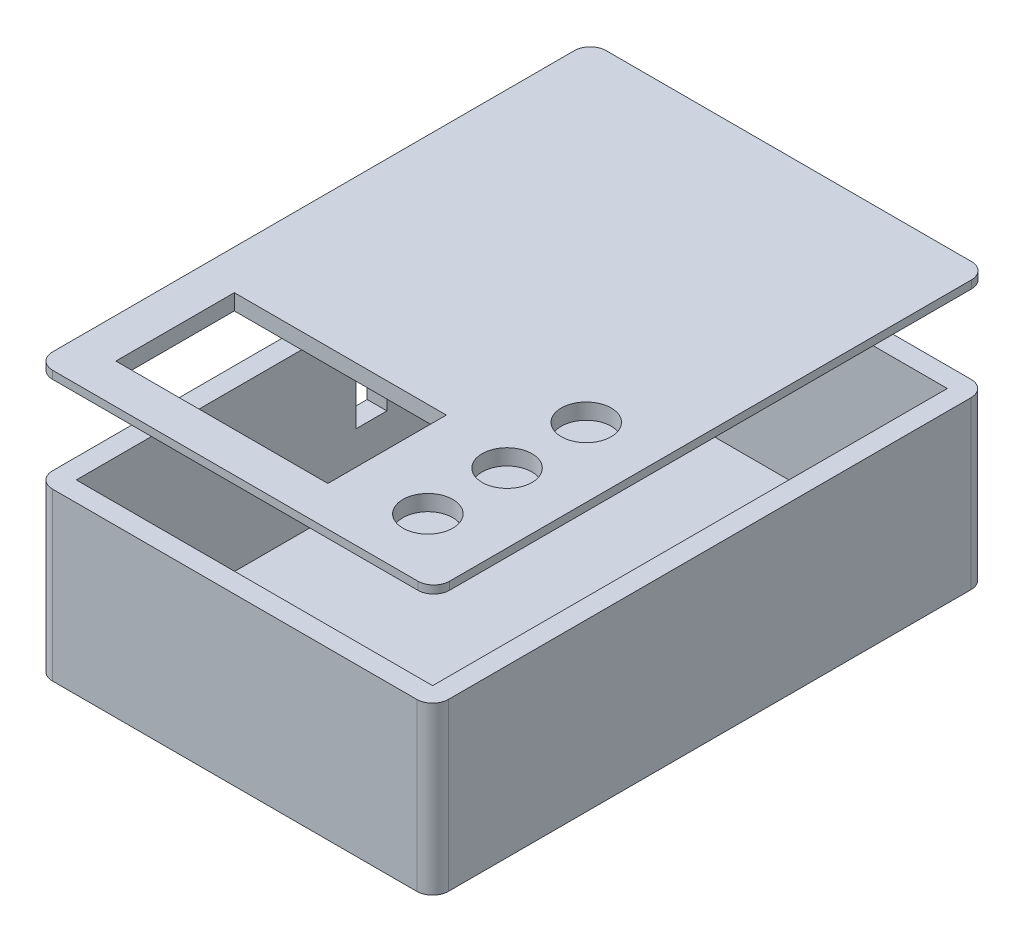
SolidWorks part; units mm, degrees
ref_plane "Front Plane" through (0, 0, 0) normal (0, 0, 1) x (1, 0, 0)
ref_plane "Top Plane" through (0, 0, 0) normal (0, 1, 0) x (1, 0, 0)
ref_plane "Right Plane" through (0, 0, 0) normal (1, 0, 0) x (0, 0, -1)
sketch "Sketch1" plane through (0, 0, 0) normal (0, 1, 0) x (1, 0, 0)
  line L1 (0, 0) -> (127, 0)
  line L2 (0, 0) -> (0, 177.8)
  line L3 (0, 177.8) -> (127, 177.8)
  line L4 (127, 0) -> (127, 177.8)
extrude "Boss-Extrude1" add sketch "Sketch1" along normal blind 50.8
sketch "Sketch2" plane through (0, 50.8, 0) normal (0, 1, 0) x (1, 0, 0)
  line L8 (6.35, 171.45) -> (6.35, 6.35)
  line L9 (6.35, 6.35) -> (120.65, 6.35)
  line L10 (120.65, 6.35) -> (120.65, 171.45)
  line L11 (120.65, 171.45) -> (6.35, 171.45)
  line L12 (6.35, 171.45) -> (6.35, 6.35)
  line L13 (6.35, 6.35) -> (120.65, 6.35)
  line L14 (120.65, 6.35) -> (120.65, 171.45)
  line L15 (120.65, 171.45) -> (6.35, 171.45)
  dimension "D1" = 6.35
extrude "Cut-Extrude1" cut sketch "Sketch2" against normal blind 50.8
ref_plane "Plane1" through (0, 78.74, 0) normal (0, 1, 0) x (1, 0, 0)
ref_plane "Plane2" through (0, 0, 0) normal (0, -1, 0) x (-1, 0, 0)
sketch "Sketch4" plane through (0, 0, 0) normal (0, -1, 0) x (-1, 0, 0)
  line L0 (0, 177.8) -> (-127, 177.8)
  line L1 (-127, 177.8) -> (0, 177.8) construction
  line L2 (-127, 0) -> (-127, 177.8) construction
  line L3 (-127, 177.8) -> (-127, 0)
  line L4 (-127, 0) -> (0, 0)
  line L5 (0, 0) -> (0, 177.8)
extrude "Boss-Extrude2" add sketch "Sketch4" along normal blind 2.54
sketch "Sketch5" plane through (0, 78.74, 0) normal (0, 1, 0) x (1, 0, 0)
  line L8 (10.16, 167.64) -> (10.16, 10.16)
  line L9 (10.16, 167.64) -> (116.84, 167.64)
  line L10 (116.84, 167.64) -> (116.84, 10.16)
  line L11 (116.84, 10.16) -> (10.16, 10.16)
extrude "Boss-Extrude3" add sketch "Sketch5" along normal blind 2.54 separate body
sketch "Sketch6" plane through (0, 81.28, 0) normal (0, 1, 0) x (1, 0, 0)
  line L0 (127.361, 0) -> (127.361, 177.5655)
  line L1 (127.361, 177.5655) -> (0, 177.5655)
  line L2 (0, 177.5655) -> (0, 0)
  line L3 (0, 0) -> (127.361, 0)
extrude "Boss-Extrude4" add sketch "Sketch6" along normal blind 2.54
sketch "Sketch7" plane through (0, 83.82, 0) normal (0, 1, 0) x (1, 0, 0)
  line L0 (0, 0) -> (0, 12.7) construction
  line L2 (0, 12.7) -> (12.7, 12.7) construction
  line L3 (0, 88.7827) -> (124.9599, 88.7827) construction
  line L4 (0, 177.5655) -> (0, 0) construction
  line L5 (0, 88.7827) -> (0, 50.7) construction
  line L6 (0, 50.7) -> (12.7, 50.7) construction
  line L7 (12.7, 50.7) -> (12.7, 12.7)
  line L8 (12.7, 12.7) -> (80.7, 12.7)
  line L9 (80.7, 12.7) -> (80.7, 50.7)
  line L10 (80.7, 50.7) -> (12.7, 50.7)
  circle A0 centre (105.1613, 20.32) radius 8
  circle A1 centre (105.1613, 45.72) radius 8
  circle A2 centre (105.1613, 71.12) radius 8
extrude "Cut-Extrude2" cut sketch "Sketch7" against normal blind 7.62
fillet "Fillet1" radius 5.08 1 edges at (127, 24.13, 0) type face fillet first side face at (63.5, 24.13, 0) second side face at (127, 24.13, -88.9)
fillet "Fillet2" radius 5.08 1 edges at (127.361, 82.55, 0) type face fillet first side face at (63.6805, 82.55, 0) second side face at (127.361, 82.55, -88.7827)
fillet "Fillet3" radius 5.08 1 edges at (127, 24.13, -177.8) type face fillet first side face at (127, 24.13, -91.44) second side face at (63.5, 24.13, -177.8)
fillet "Fillet4" radius 5.08 1 edges at (0, 24.13, -177.8) type face fillet first side face at (60.96, 24.13, -177.8) second side face at (0, 24.13, -88.9)
fillet "Fillet5" radius 5.08 1 edges at (0, 24.13, 0) type face fillet first side face at (0, 24.13, -86.36) second side face at (60.96, 24.13, 0)
fillet "Fillet6" radius 5.08 1 edges at (127.361, 82.55, -177.5655) type face fillet first side face at (127.361, 82.55, -91.3227) second side face at (63.6805, 82.55, -177.5655)
fillet "Fillet7" radius 5.08 1 edges at (0, 82.55, -177.5655) type face fillet first side face at (61.1405, 82.55, -177.5655) second side face at (0, 82.55, -88.7827)
fillet "Fillet8" radius 5.08 1 edges at (0, 82.55, 0) type face fillet first side face at (0, 82.55, -86.2427) second side face at (61.1405, 82.55, 0)
sketch "Sketch8" plane through (0, 0, 0) normal (0, 1, 0) x (1, 0, 0)
  line L0 (6.35, 171.45) -> (6.35, 88.9) construction
  line L1 (6.35, 171.45) -> (6.35, 6.35) construction
  line L2 (6.35, 88.9) -> (123.6465, 88.9) construction
sketch "Sketch9" plane through (0, 0, -177.8) normal (0, 0, -1) x (-1, 0, 0)
  line L0 (-121.92, 50.8) -> (-5.08, 50.8) construction
  line L1 (-63.5, 50.8) -> (-63.5, 38.1) construction
  line L2 (-63.5, 38.1) -> (-50.8444, 38.1) construction
  line L3 (-63.5, 38.1) -> (-76.2, 38.1) construction
  line L4 (-50.8444, 38.1) -> (-76.2, 38.1) construction
  line L5 (-50.8444, 32.9548) -> (-76.2, 32.9548)
  line L6 (-50.8444, 43.2452) -> (-76.2, 43.2452)
  arc A0 (-50.8444, 32.9548) -> (-50.8444, 43.2452) centre (-50.8444, 38.1) ccw
  arc A1 (-76.2, 43.2452) -> (-76.2, 32.9548) centre (-76.2, 38.1) ccw
  point P6 (-63.5222, 38.1)
extrude "Cut-Extrude3" cut sketch "Sketch9" against normal blind 5.08 contours A1 L5 A0 L6
sketch "Sketch10" plane through (0, 0, 0) normal (-1, 0, 0) x (0, 0, 1)
  line L0 (-172.72, 50.8) -> (-147.4141, 50.8) construction
  line L1 (-172.72, 50.8) -> (-5.08, 50.8) construction
  line L2 (-147.4141, 50.8) -> (-127.0941, 50.8) construction
  line L4 (-144.8741, 20.1468) -> (-152.8741, 20.1468)
  line L5 (-152.8741, 20.1468) -> (-152.8741, 36.1468)
  line L6 (-144.8741, 20.1468) -> (-142.8741, 20.1468)
  line L7 (-142.8741, 20.1468) -> (-142.8741, 36.1468)
  line L8 (-142.8741, 36.1468) -> (-152.8741, 36.1468)
  line L9 (-127.0941, 20.1468) -> (-137.1741, 20.1468)
  line L10 (-137.1741, 20.1468) -> (-137.1741, 36.1468)
  line L11 (-137.1741, 36.1468) -> (-127.1741, 36.1468)
  line L12 (-127.1741, 36.1468) -> (-127.1741, 20.1468)
  line L13 (-127.1741, 20.1468) -> (-127.0941, 20.1468)
  line L15 (-121.5861, 36.1468) -> (-121.5861, 20.1468)
  line L16 (-121.5861, 20.1468) -> (-111.5861, 20.1468)
  line L17 (-111.5861, 20.1468) -> (-111.5861, 36.1468)
  line L18 (-111.5861, 36.1468) -> (-121.5861, 36.1468)
  line L20 (-105.9981, 36.1468) -> (-105.9981, 20.1468)
  line L21 (-105.9981, 20.1468) -> (-95.9981, 20.1468)
  line L22 (-95.9981, 20.1468) -> (-95.9981, 36.1468)
  line L23 (-95.9981, 36.1468) -> (-105.9981, 36.1468)
extrude "Cut-Extrude5" cut sketch "Sketch10" against normal blind 10.16 contours L8 L5 L4 L6 L7
extrude "Cut-Extrude6" cut sketch "Sketch10<3>" against normal blind 10.16 contours L12 L11 L10 L9 | L17 L18 L15 L16 | L22 L23 L20 L21 region at (0, 28.1468, -132.1741) region at (0, 28.1468, -116.5861) region at (0, 28.1468, -100.9981)
sketch "Sketch10<3>" plane through (0, 0, 0) normal (-1, 0, 0) x (0, 0, 1) same geometry as "Sketch10"
sketch "Sketch12" plane through (0, 0, 0) normal (0, 1, 0) x (1, 0, 0)
  line L0 (6.35, 88.9) -> (12.7, 88.9) construction
  line L1 (12.7, 88.9) -> (12.7, 95.25) construction
  line L2 (6.35, 171.45) -> (12.7, 171.45) construction
  line L3 (120.65, 171.45) -> (6.35, 171.45) construction
  line L4 (12.7, 171.45) -> (12.7, 165.1) construction
  line L5 (120.65, 171.45) -> (120.65, 165.1) construction
  line L6 (120.65, 6.35) -> (120.65, 171.45) construction
  line L7 (120.65, 165.1) -> (114.3, 165.1) construction
  line L8 (114.3, 88.9) -> (114.3, 95.25) construction
  circle A0 centre (114.3, 95.25) radius 2.4221
  circle A1 centre (114.3, 95.25) radius 3.7165
  circle A2 centre (12.7, 95.25) radius 2.54
  circle A3 centre (12.7, 95.25) radius 3.81
  circle A4 centre (12.7, 165.1) radius 2.54
  circle A5 centre (12.7, 165.1) radius 3.81
  circle A6 centre (114.3, 165.1) radius 2.54
  circle A7 centre (114.3, 165.1) radius 3.81
extrude "Boss-Extrude5" add sketch "Sketch12" along normal blind 7.62
sketch "Sketch14" plane through (0, 0, 0) normal (0, 1, 0) x (1, 0, 0)
  circle A0 centre (114.3, 95.25) radius 2.4221
extrude "Cut-Extrude7" cut sketch "Sketch14" against normal blind 2.54
sketch "Sketch15" plane through (0, 0, 0) normal (0, 1, 0) x (1, 0, 0)
  circle A0 centre (114.3, 165.1) radius 2.54
extrude "Cut-Extrude8" cut sketch "Sketch15" against normal blind 2.54
sketch "Sketch16" plane through (0, 0, 0) normal (0, 1, 0) x (1, 0, 0)
  circle A0 centre (12.7, 165.1) radius 2.54
extrude "Cut-Extrude9" cut sketch "Sketch16" against normal blind 2.54
sketch "Sketch17" plane through (0, 0, 0) normal (0, 1, 0) x (1, 0, 0)
  circle A0 centre (12.7, 95.25) radius 2.54
extrude "Cut-Extrude10" cut sketch "Sketch17" against normal blind 2.54
